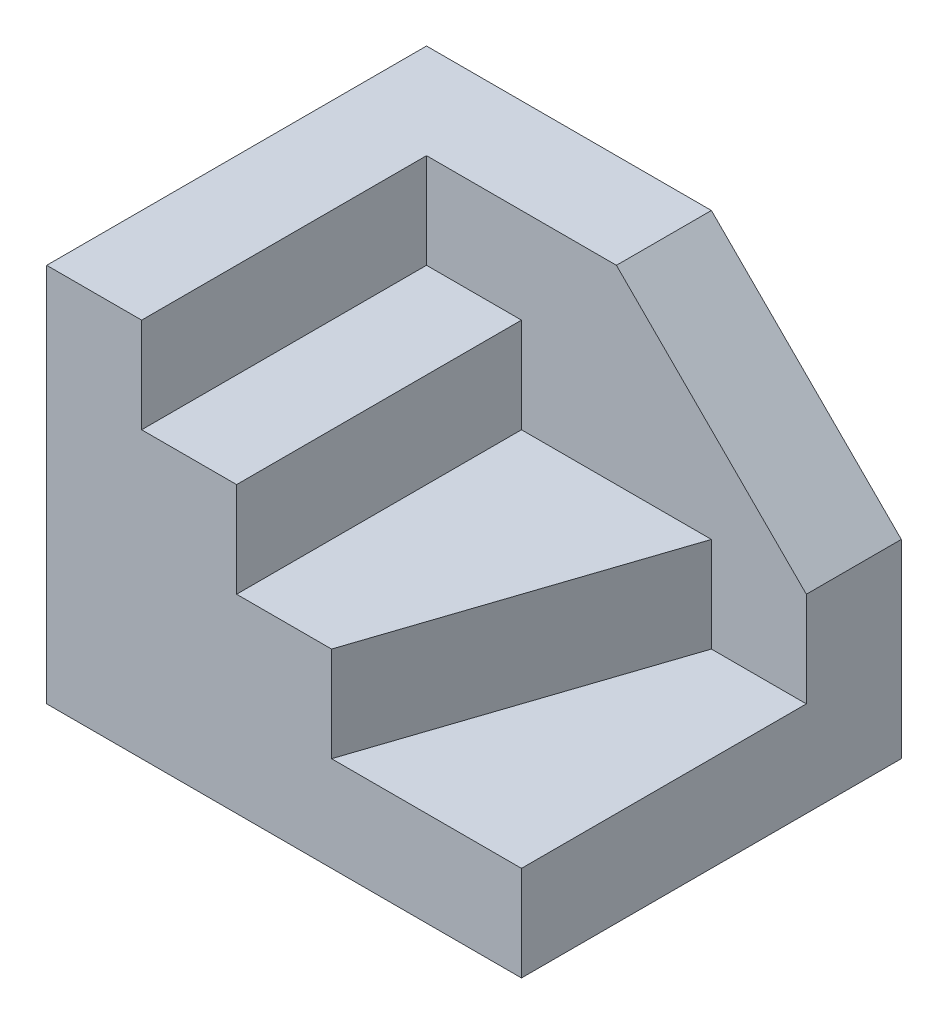
SolidWorks part; units mm, degrees
ref_plane "Front Plane" through (0, 0, 0) normal (0, 0, 1) x (1, 0, 0)
ref_plane "Top Plane" through (0, 0, 0) normal (0, 1, 0) x (1, 0, 0)
ref_plane "Right Plane" through (0, 0, 0) normal (1, 0, 0) x (0, 0, -1)
sketch "Sketch1" plane through (0, 0, 0) normal (0, 1, 0) x (1, 0, 0)
  line L0 (10, 0) -> (10, 30)
  line L1 (0, 0) -> (50, 0)
  line L2 (0, 0) -> (0, 40)
  line L3 (0, 40) -> (50, 40)
  line L4 (50, 0) -> (50, 40)
  line L5 (10, 30) -> (50, 30)
  line L6 (20, 0) -> (20, 30)
  line L7 (30, 0) -> (40, 30)
  dimension "D1" = 40
  dimension "D2" = 50
  dimension "D3" = 10
  dimension "D4" = 10
  dimension "D5" = 10
  dimension "D6" = 20
  dimension "D7" = 10
extrude "Boss-Extrude1" add sketch "Sketch1" along normal blind 40 contours L0 L5 L4 L3 L2 L1 region at (5, 0, -0.6403)
extrude "Boss-Extrude2" add sketch "Sketch1<7>" along normal blind 30 contours L1 L6 L5 L0 region at (15, 0, -15)
sketch "Sketch1<7>" plane through (0, 0, 0) normal (0, 1, 0) x (1, 0, 0) same geometry as "Sketch1"
extrude "Boss-Extrude3" add sketch "Sketch1<8>" along normal blind 20 contours L1 L7 L5 L6 region at (27.7778, 0, -16.6667)
sketch "Sketch1<8>" plane through (0, 0, 0) normal (0, 1, 0) x (1, 0, 0) same geometry as "Sketch1"
extrude "Boss-Extrude4" add sketch "Sketch1<9>" along normal blind 10 contours L7 L1 L4 L5 region at (42.2222, 0, -13.3333)
sketch "Sketch1<9>" plane through (0, 0, 0) normal (0, 1, 0) x (1, 0, 0) same geometry as "Sketch1"
chamfer "Chamfer1" distance 20 angle 45 1 edges at (50, 40, -35)
